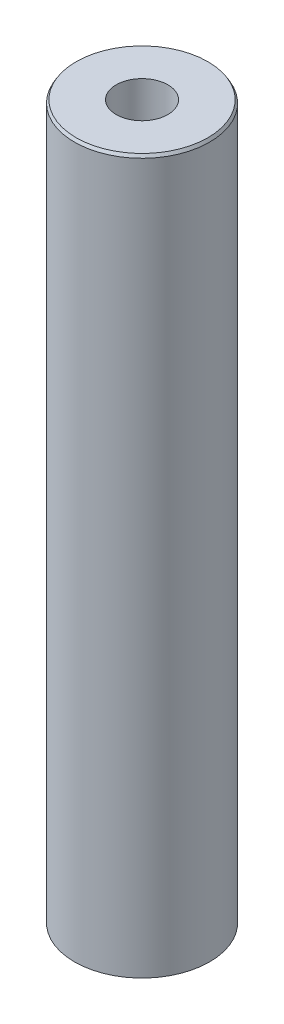
SolidWorks part; units mm, degrees
ref_plane "Front Plane" through (0, 0, 0) normal (0, 0, 1) x (1, 0, 0)
ref_plane "Top Plane" through (0, 0, 0) normal (0, 1, 0) x (1, 0, 0)
ref_plane "Right Plane" through (0, 0, 0) normal (1, 0, 0) x (0, 0, -1)
sketch "Sketch1" plane through (0, 0, 0) normal (0, 1, 0) x (1, 0, 0)
  circle A0 centre (0, 0) radius 17.5
  dimension "SHAFT_OD" = 35
extrude "Boss-Extrude1" add sketch "Sketch1" along normal blind 185.0147
sketch "Sketch2" plane through (0, 0, 0) normal (0, 1, 0) x (1, 0, 0)
  circle A0 centre (0, 0) radius 6.6901
  dimension "BORE_D" = 13.3802
extrude "Cut-Extrude1" cut sketch "Sketch2" along normal through all
chamfer "Chamfer1" distance 0.7708 angle 30 2 edges at (0, 185.0147, 17.5) (0, 0, 17.5) first distance on face at (0, 185.0147, 17.5) first distance on face at (0, 0, 6.6901)
